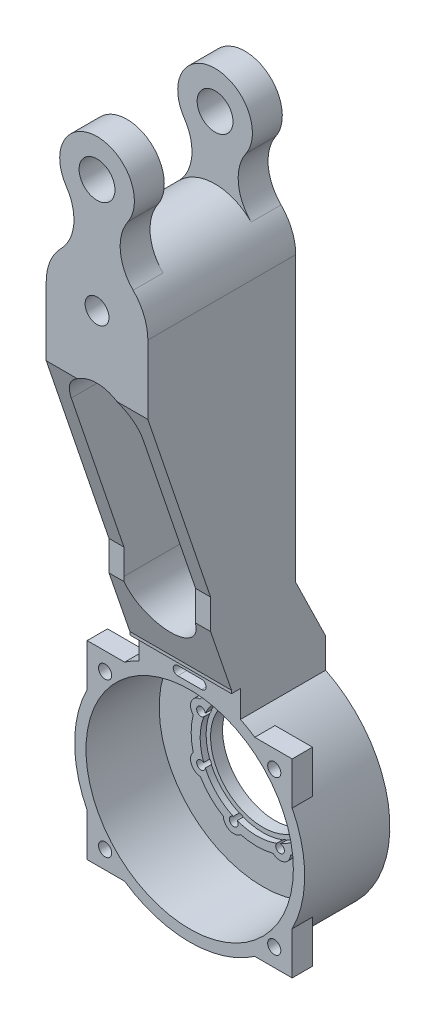
SolidWorks part; units mm, degrees
material "ABS"
ref_plane "Front Plane" through (0, 0, 0) normal (0, 0, 1) x (1, 0, 0)
ref_plane "Top Plane" through (0, 0, 0) normal (0, 1, 0) x (1, 0, 0)
ref_plane "Right Plane" through (0, 0, 0) normal (1, 0, 0) x (0, 0, -1)
sketch "Sketch1" plane through (0, 0, 0) normal (0, 0, 1) x (1, 0, 0)
  line L0 (0, 55.6228) -> (0, -56.75) construction
  line L1 (-58.5265, 0) -> (65.4088, 0) construction
  line L2 (-17, 34.5435) -> (-17, 43.5)
  line L3 (-17, 43.5) -> (17, 43.5)
  line L4 (17, 43.5) -> (17, 34.5435)
  circle A0 centre (0, 0) radius 33.5 construction
  circle A1 centre (0, 0) radius 34.7
  arc A2 (-17, 34.5435) -> (17, 34.5435) centre (0, 0) ccw
  circle A4 centre (0, 0) radius 20.25 construction
  circle A7 centre (0, 0) radius 17.5
  circle A8 centre (-7.7493, 18.7086) radius 1.45
  circle A9 centre (7.7493, 18.7086) radius 1.45
  circle A10 centre (18.7086, 7.7493) radius 1.45
  circle A11 centre (18.7086, -7.7493) radius 1.45
  circle A12 centre (7.7493, -18.7086) radius 1.45
  circle A13 centre (-7.7493, -18.7086) radius 1.45
  circle A14 centre (-18.7086, -7.7493) radius 1.45
  circle A15 centre (-18.7086, 7.7493) radius 1.45
  point P32 (0, 0)
  dimension "D1" = 67
  dimension "D7" = 40.5
  dimension "D10" = 35
  dimension "D6" = 2.9
  dimension "D9" = 38.5
  dimension "D2" = 5
  dimension "D3" = 1.2
  dimension "D4" = 34
  dimension "D5" = 10
  dimension "D8" = 8
extrude "FrontPanel" add sketch "Sketch1" along normal blind 4 contours L2 A2 L4 L3 A1 | A1 A15 A14 A13 A12 A11 A10 A9 A8 A7 region at (-15.8751, 39.0217, 0) region at (-33.7185, 0, 0)
extrude "SideWalls" add sketch "Sketch1<3>" along normal blind 28.5 contours L2 A2 L4 L3 A1 region at (-15.8751, 39.0217, 0)
sketch "Sketch1<3>" plane through (0, 0, 0) normal (0, 0, 1) x (1, 0, 0) same geometry as "Sketch1"
sketch "Sketch2" plane through (0, 0, 4) normal (0, 0, 1) x (1, 0, 0)
  arc A0 (-5.4209, 21.3217) -> (-11.2435, 18.9099) centre (-7.7493, 18.7086) ccw
  circle A1 centre (0, 0) radius 20.25 construction
  circle A2 centre (0, 0) radius 19
  arc A3 (-11.2435, 18.9099) -> (-18.9099, 11.2435) centre (0, 0) ccw
  arc A4 (11.2435, 18.9099) -> (5.4209, 21.3217) centre (7.7493, 18.7086) ccw
  arc A5 (21.3217, 5.4209) -> (18.9099, 11.2435) centre (18.7086, 7.7493) ccw
  arc A6 (18.9099, -11.2435) -> (21.3217, -5.4209) centre (18.7086, -7.7493) ccw
  arc A7 (5.4209, -21.3217) -> (11.2435, -18.9099) centre (7.7493, -18.7086) ccw
  arc A8 (-11.2435, -18.9099) -> (-5.4209, -21.3217) centre (-7.7493, -18.7086) ccw
  arc A9 (-21.3217, -5.4209) -> (-18.9099, -11.2435) centre (-18.7086, -7.7493) ccw
  arc A10 (-18.9099, 11.2435) -> (-21.3217, 5.4209) centre (-18.7086, 7.7493) ccw
  arc A11 (5.4209, 21.3217) -> (-5.4209, 21.3217) centre (0, 0) ccw
  arc A12 (18.9099, 11.2435) -> (11.2435, 18.9099) centre (0, 0) ccw
  arc A13 (21.3217, -5.4209) -> (21.3217, 5.4209) centre (0, 0) ccw
  arc A14 (11.2435, -18.9099) -> (18.9099, -11.2435) centre (0, 0) ccw
  arc A15 (-5.4209, -21.3217) -> (5.4209, -21.3217) centre (0, 0) ccw
  arc A16 (-18.9099, -11.2435) -> (-11.2435, -18.9099) centre (0, 0) ccw
  arc A17 (-21.3217, 5.4209) -> (-21.3217, -5.4209) centre (0, 0) ccw
  point P32 (0, 0)
  dimension "D1" = 7
  dimension "D2" = 38
  dimension "D3" = 3
  dimension "D4" = 8
extrude "MotorSpacer" add sketch "Sketch2" along normal blind 2
extrude "MotorMountingHoles" cut sketch "Sketch1<5>" along normal blind 6 contours A15 | A14 | A13 | A12 | A11 | A10 | A9 | A8
sketch "Sketch1<5>" plane through (0, 0, 0) normal (0, 0, 1) x (1, 0, 0) same geometry as "Sketch1"
sketch "Sketch3" plane through (0, 0, 28.5) normal (0, 0, 1) x (1, 0, 0)
  line L0 (-58.5265, 0) -> (65.4088, 0) construction
  line L1 (0, 55.6228) -> (0, -56.75) construction
  line L2 (0, 51.8514) -> (0, -45.3103) construction
  line L3 (-50.1667, 0) -> (45.3988, 0) construction
  line L4 (-34.3, 31.75) -> (-21.7758, 31.75)
  line L5 (34.3, 31.75) -> (21.7758, 31.75)
  line L7 (34.3, 31.75) -> (34.3, 17.486)
  line L8 (-34.3, 31.75) -> (-34.3, 17.486)
  line L9 (-34.3, -31.75) -> (-21.7758, -31.75)
  line L10 (-34.3, -31.75) -> (-34.3, -17.486)
  line L11 (34.3, -31.75) -> (21.7758, -31.75)
  line L12 (34.3, -31.75) -> (34.3, -17.486)
  circle A18 centre (-28.3, 25.75) radius 2.2
  arc A45 (21.7758, 31.75) -> (34.3, 17.486) centre (0, 0) cw
  arc A47 (-17, 34.5435) -> (17, 34.5435) centre (0, 0) ccw construction
  circle A48 centre (28.3, 25.75) radius 2.2
  arc A49 (-21.7758, 31.75) -> (-34.3, 17.486) centre (0, 0) ccw
  arc A50 (-21.7758, -31.75) -> (-34.3, -17.486) centre (0, 0) cw
  circle A51 centre (-28.3, -25.75) radius 2.2
  circle A52 centre (28.3, -25.75) radius 2.2
  arc A53 (21.7758, -31.75) -> (34.3, -17.486) centre (0, 0) ccw
  arc M14 (-17, 34.5435) -> (17, 34.5435) centre (0, 0) ccw
  dimension "D3" = 4.4
  dimension "D4" = 6
  dimension "D5" = 6
  dimension "D1" = 28.3
  dimension "D2" = 25.75
extrude "Boss-Extrude7" add sketch "Sketch3" against normal blind 6.8 contours A18 L4 L8 M14 | A48 L7 L5 M14 | A52 L11 L12 M14 | A51 L10 L9 M14 | A18 | A51 | A52 | A48 region at (30.6142, 27.5086, 28.5) region at (30.6142, -27.5086, 28.5) region at (-30.6142, -27.5086, 28.5) region at (-30.6142, 27.5086, 28.5)
extrude "Cut-Extrude2" cut sketch "Sketch3<5>" against normal blind 6 contours A18 | A48 | A52 | A51
sketch "Sketch3<5>" plane through (0, 0, 28.5) normal (0, 0, 1) x (1, 0, 0) same geometry as "Sketch3"
sketch "Sketch7" plane through (0, 0, 28.5) normal (0, 0, 1) x (1, 0, 0)
  line L0 (-4, 38.2) -> (4, 38.2) construction
  line L5 (0, 51.8514) -> (0, -45.3103) construction
  line L6 (-4, 39.7) -> (4, 39.7)
  line L7 (-4, 36.7) -> (4, 36.7)
  arc A7 (-4, 39.7) -> (-4, 36.7) centre (-4, 38.2) ccw
  arc A8 (4, 36.7) -> (4, 39.7) centre (4, 38.2) ccw
  circle A13 centre (0, 0) radius 34.7 construction
  point P4 (0, 38.2)
  dimension "D4" = 11
  dimension "D1" = 3
  dimension "D2" = 8
  dimension "D3" = 2
ref_plane "Plane2" through (0, 34.7, 0) normal (0, -1, 0) x (-1, 0, 0)
sketch "Sketch9" plane through (0, 34.7, 0) normal (0, -1, 0) x (-1, 0, 0)
  line L0 (38.5, 0) -> (-38.5, 0) construction
  line L1 (-6.5, 0) -> (6.5, 0)
  line L2 (-6.5, -3.2) -> (-6.5, -8)
  line L3 (-6.5, -8) -> (6.5, -8)
  line L4 (6.5, -3.2) -> (6.5, -8)
  line L5 (-6.5, -3.2) -> (-8, -3.2)
  line L6 (-8, -3.2) -> (-6.5, 0)
  line L7 (-11.2435, -4) -> (-5.4209, -4) construction
  line L10 (0, 6.8938) -> (0, -12.2231) construction
  line L11 (6.5, 0) -> (8, -3.2)
  line L12 (8, -3.2) -> (6.5, -3.2)
  point P0 (0, -4)
  dimension "D1" = 13
  dimension "D2" = 4
  dimension "D3" = 1.5
  dimension "D4" = 3.2
  dimension "D5" = 13
extrude "Cut-Extrude8" cut sketch "Sketch7" against normal through all
ref_plane "Plane3" through (0, 0, 5) normal (0, 0, -1) x (-1, 0, 0)
sketch "Sketch10" plane through (0, 0, 5) normal (0, 0, -1) x (-1, 0, 0)
  circle A0 centre (0, 0) radius 62 construction
  dimension "D1" = 124
ref_plane "Plane4" through (0, 65, 0) normal (0, 1, 0) x (1, 0, 0)
sketch "Sketch11" plane through (0, 65, 0) normal (0, 1, 0) x (1, 0, 0)
  line L0 (-17, -28.5) -> (-17, 0) construction
  line L5 (-17, -10) -> (17, -10)
  line L6 (-17, -10) -> (-17, -38.5)
  line L7 (-17, -38.5) -> (17, -38.5)
  line L8 (17, -10) -> (17, -38.5)
  line L9 (62, -5) -> (-62, -5) construction
  line L10 (-17, -28.5) -> (-17, 0) construction
  line L11 (17, -28.5) -> (17, 0) construction
  dimension "D1" = 5
extrude "Boss-Extrude8" add sketch "Sketch11" along normal blind 10 separate body
sketch "Sketch14" plane through (0, 43.5, 0) normal (0, 1, 0) x (1, 0, 0)
  line L0 (17, -38.5) -> (17, -10) construction
  line L1 (-17, 0) -> (17, 0)
  line L2 (-17, 0) -> (-17, -31.5)
  line L3 (-17, -31.5) -> (17, -31.5)
  line L4 (17, 0) -> (17, -31.5)
  line L5 (17, -28.5) -> (21.7758, -28.5) construction
  dimension "D1" = 3
extrude "Boss-Extrude9" add sketch "Sketch14" along normal blind 1 contours L2 L3 L4 L1
loft "Loft5" add section face at (0, 44.5, 15.75) section face at (0, 65, 24.25) connector at (17, 44.5, 31.5) connector at (17, 65, 38.5)
extrude "Cut-Extrude11" cut sketch "Sketch9" against normal blind 16 and the other way blind 1
sketch "Sketch19" plane through (0, 0, 10) normal (0, 0, -1) x (-1, 0, 0)
  line L2 (-17, 75) -> (17, 75)
  line L3 (-17, 75) -> (-17, 160)
  line L4 (17, 160) -> (17, 75)
  line L5 (0, 198) -> (0, 160) construction
  line L7 (-17, 143) -> (17, 143) construction
  line L12 (0, 127) -> (0, 66.5) construction
  line L13 (12, 127) -> (12, 66.5)
  line L14 (-12, 127) -> (-12, 66.5)
  line L15 (17, 44.5) -> (-17, 44.5) construction
  arc A5 (-17, 160) -> (-12.076, 171.9654) centre (0, 160) cw
  circle A6 centre (0, 198) radius 6
  arc A7 (10.3324, 190.965) -> (-10.3324, 190.965) centre (0, 198) ccw
  circle A8 centre (0, 160) radius 4
  arc A10 (10.3324, 190.965) -> (12.076, 171.9654) centre (22.7313, 182.523) ccw
  arc A11 (-10.3324, 190.965) -> (-12.076, 171.9654) centre (-22.7313, 182.523) cw
  arc A12 (12.076, 171.9654) -> (17, 160) centre (0, 160) cw
  circle A13 centre (0, 160) radius 17 construction
  arc A15 (-12.076, 171.9654) -> (12.076, 171.9654) centre (0, 160) cw
  arc A19 (-17, 34.5435) -> (17, 34.5435) centre (0, 0) ccw construction
  arc A20 (12, 127) -> (-12, 127) centre (0, 127) ccw
  arc A21 (-12, 66.5) -> (12, 66.5) centre (0, 66.5) ccw
  point P27 (0, -38.5)
  point P30 (0, 96.75)
  point P35 (0, 54.5)
  line M3 (-17, 65) -> (17, 65)
  dimension "D1" = 8
  dimension "D4" = 25
  dimension "D5" = 12
  dimension "D6" = 30
  dimension "D7" = 17
  dimension "D8" = 4
  dimension "D9" = 249
  dimension "D2" = 160
  dimension "D3" = 38
  dimension "D10" = 5
  dimension "D11" = 10
extrude "Boss-Extrude10" add sketch "Sketch19" against normal blind 49.5 contours A8 | A6 | A6 | L4 L2 L3 A5 A11 A7 A10 A12 region at (0, 198, 10) region at (0, 160, 10)
sketch "Sketch21" plane through (17, 0, 0) normal (1, 0, 0) x (0, 0, -1)
  line L0 (-38.5, 75) -> (-59.5, 75)
  line L1 (-59.5, 75) -> (-59.5, 137)
  line L2 (-59.5, 75) -> (-59.5, 160) construction
  line L3 (-59.5, 137) -> (-38.5, 75)
  line L6 (-10, 143) -> (-59.5, 143) construction
  dimension "D1" = 6
  dimension "D2" = 62
extrude "Cut-Extrude12" cut sketch "Sketch21" against normal up to next contours L3 L0 L1
extrude "Cut-Extrude14" cut sketch "Sketch19<5>" against normal through all from offset 5 contours L13 A20 L14 L2 | L14 A21 L13 L2 M3 | A21 M3 region at (0, 105.7708, 10) region at (0, 70.0018, 10) region at (0, 60.5874, 10) offset against normal yes
sketch "Sketch19<5>" plane through (0, 0, 10) normal (0, 0, -1) x (-1, 0, 0) same geometry as "Sketch19"
extrude "Cut-Extrude15" cut sketch "Sketch19<6>" against normal offset from surface (29.5 mm away) 10 from offset 10 contours A11 A15 A10 A7 A6 region at (7.3367, 181.1103, 10) up to face at (-6, 198, 59.5) offset against normal yes
sketch "Sketch19<6>" plane through (0, 0, 10) normal (0, 0, -1) x (-1, 0, 0) same geometry as "Sketch19"
equation "\"MotorDismetr\"= 67"
equation "\"D1@Sketch1\"=\"MotorDismetr\""
equation "\"M3ForThread\"=4"
